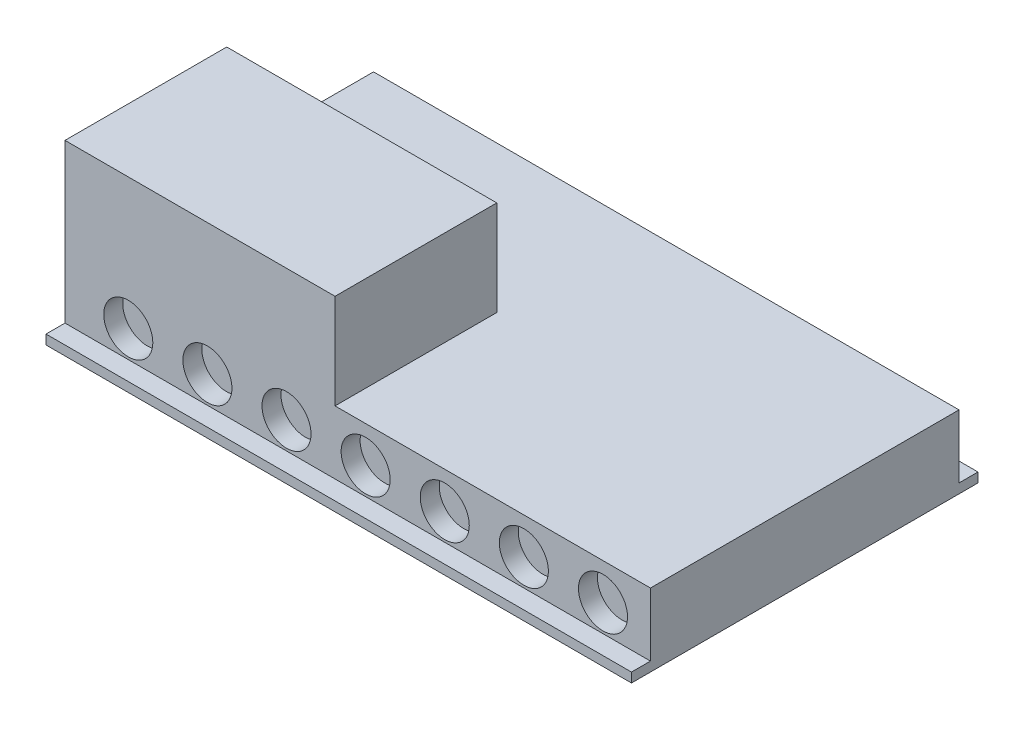
SolidWorks part; units mm, degrees
ref_plane "Front Plane" through (0, 0, 0) normal (0, 0, 1) x (1, 0, 0)
ref_plane "Top Plane" through (0, 0, 0) normal (0, 1, 0) x (1, 0, 0)
ref_plane "Right Plane" through (0, 0, 0) normal (1, 0, 0) x (0, 0, -1)
sketch "Sketch1" plane through (0, 0, 0) normal (0, 1, 0) x (1, 0, 0)
  line L1 (0, 0) -> (185, 0)
  line L2 (0, 0) -> (0, 97.5)
  line L3 (0, 97.5) -> (185, 97.5)
  line L4 (185, 0) -> (185, 97.5)
  dimension "D1" = 185
extrude "Boss-Extrude1" add sketch "Sketch1" along normal blind 23
sketch "Sketch7" plane through (0, 23, 0) normal (0, 1, 0) x (1, 0, 0)
  line L1 (0, 0) -> (85.3301, 0)
  line L2 (0, 0) -> (0, 51.1085)
  line L3 (0, 51.1085) -> (85.3301, 51.1085)
  line L4 (85.3301, 0) -> (85.3301, 51.1085)
extrude "Boss-Extrude5" add sketch "Sketch7" along normal blind 30
shell "Shell5" [suppressed] thickness 3
sketch "Sketch9" plane through (0, 0, 0) normal (0, 0, 1) x (1, 0, 0)
  line L0 (185, 23) -> (185, 0) construction
  line L1 (0, 0) -> (185, 0)
  line L2 (0, 0) -> (0, 3)
  line L3 (0, 3) -> (185, 3)
  line L4 (185, 0) -> (185, 3)
extrude "Boss-Extrude6" add sketch "Sketch9" along normal blind 6
sketch "Sketch10" plane through (0, 0, -97.5) normal (0, 0, -1) x (-1, 0, 0)
  line L1 (-185, 0) -> (0, 0)
  line L2 (-185, 0) -> (-185, 3)
  line L3 (-185, 3) -> (0, 3)
  line L4 (0, 0) -> (0, 3)
extrude "Boss-Extrude7" add sketch "Sketch10" along normal blind 6
sketch "Sketch11" plane through (0, 0, 0) normal (0, 0, 1) x (1, 0, 0)
  circle A0 centre (170, 11.5) radius 7.75
  circle A1 centre (145, 11.5) radius 7.75
  circle A2 centre (120, 11.5) radius 7.75
  circle A3 centre (95, 11.5) radius 7.75
  circle A4 centre (70, 11.5) radius 7.75
  circle A5 centre (45, 11.5) radius 7.75
  circle A6 centre (20, 11.5) radius 7.75
extrude "Cut-Extrude2" cut sketch "Sketch11" against normal blind 6
